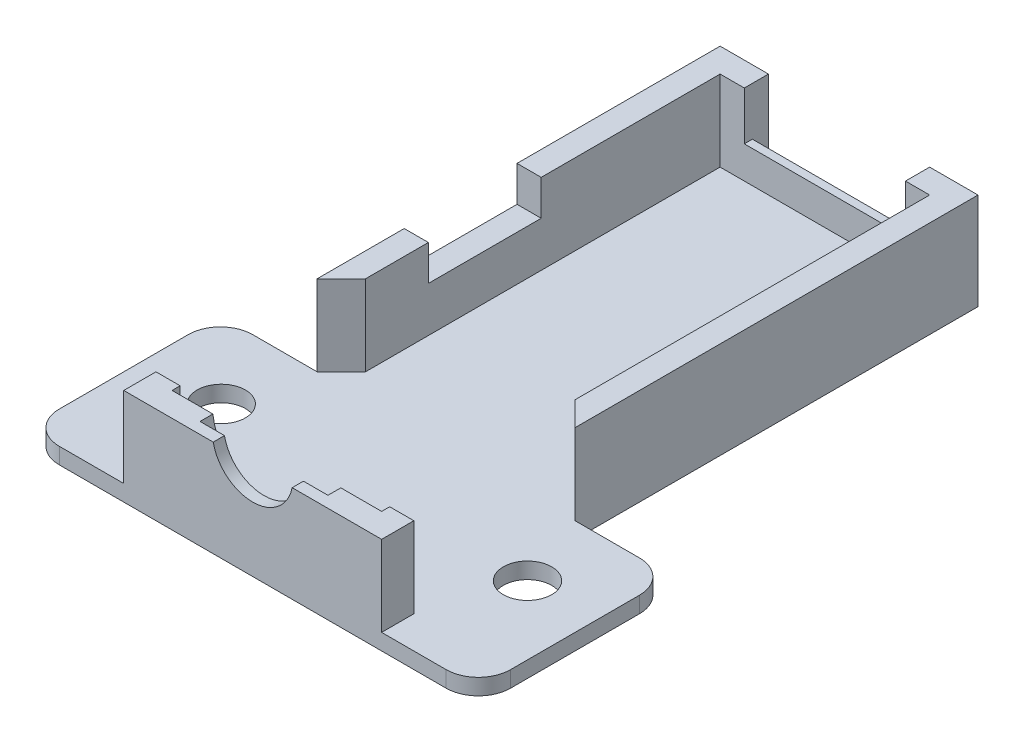
SolidWorks part; units mm, degrees
ref_plane "Front Plane" through (0, 0, 0) normal (0, 0, 1) x (1, 0, 0)
ref_plane "Top Plane" through (0, 0, 0) normal (0, 1, 0) x (1, 0, 0)
ref_plane "Right Plane" through (0, 0, 0) normal (1, 0, 0) x (0, 0, -1)
sketch "Sketch1" plane through (0, 0, 0) normal (0, 1, 0) x (1, 0, 0)
  line L1 (-6.5, 17) -> (6.5, 17)
  line L2 (-6.5, 17) -> (-6.5, -17)
  line L3 (-6.5, -17) -> (6.5, -17)
  line L4 (6.5, 17) -> (6.5, -17)
  line L5 (-6.5, 17) -> (6.5, -17) construction
  line L6 (-6.5, -17) -> (6.5, 17) construction
  line L7 (-8, 18.5) -> (8, 18.5)
  line L8 (-8, 18.5) -> (-8, -18.5)
  line L9 (-8, -18.5) -> (8, -18.5)
  line L10 (8, 18.5) -> (8, -18.5)
  line L11 (-8, 18.5) -> (8, -18.5) construction
  line L12 (-8, -18.5) -> (8, 18.5) construction
  point P0 (0, 0)
  point P6 (0, 0)
  dimension "D1" = 13
  dimension "D2" = 1.5
  dimension "D3" = 1.5
  dimension "D4" = 34
extrude "Boss-Extrude1" add sketch "Sketch1" along normal blind 5 contours L7 L10 L9 L8 | L2 L3 L4 L1
sketch "Sketch2" plane through (0, 0, 0) normal (0, -1, 0) x (1, 0, 0)
  line L1 (8, -18.5) -> (-8, -18.5)
  line L2 (8, -18.5) -> (8, 18.5)
  line L3 (8, 18.5) -> (-8, 18.5)
  line L4 (-8, -18.5) -> (-8, 18.5)
  line L5 (8, -18.5) -> (-8, 18.5) construction
  line L6 (8, 18.5) -> (-8, -18.5) construction
  point P0 (0, 0)
extrude "Boss-Extrude2" add sketch "Sketch2" along normal blind 1
sketch "Sketch3" plane through (8, 0, 0) normal (1, 0, 0) x (0, 0, -1)
  line L0 (18.5, 5) -> (-18.5, 5) construction
  line L1 (-16.5, 0) -> (-6.5, 0)
  line L2 (-16.5, 0) -> (-16.5, 5)
  line L3 (-16.5, 5) -> (-6.5, 5)
  line L4 (-6.5, 0) -> (-6.5, 5)
  line L5 (-18.5, 5) -> (-18.5, -1) construction
  dimension "D1" = 2
  dimension "D2" = 10
extrude "Cut-Extrude1" cut sketch "Sketch3" against normal blind 21
sketch "Sketch4" plane through (-8, 0, 0) normal (-1, 0, 0) x (0, 0, 1)
  line L0 (16.5, 0) -> (6.5, 0) construction
  line L1 (1.1, 2.8) -> (-5.9, 2.8)
  line L2 (1.1, 2.8) -> (1.1, 5)
  line L3 (1.1, 5) -> (-5.9, 5)
  line L4 (-5.9, 2.8) -> (-5.9, 5)
  line L5 (-18.5, 5) -> (6.5, 5) construction
  line L6 (6.5, 0) -> (6.5, 5) construction
  dimension "D1" = 2.8
  dimension "D2" = 0
  dimension "D3" = 7
  dimension "D4" = 5.4
extrude "Cut-Extrude2" cut sketch "Sketch4" against normal blind 2
sketch "Sketch5" plane through (0, 0, 18.5) normal (0, 0, 1) x (1, 0, 0)
  line L0 (8, -1) -> (-8, -1) construction
  circle A0 centre (0, 5.5) radius 2.5
  dimension "D1" = 5
  dimension "D2" = 6.5
extrude "Cut-Extrude3" cut sketch "Sketch5" against normal blind 2
sketch "Sketch6" plane through (0, 0, -17) normal (0, 0, 1) x (1, 0, 0)
  line L0 (-6.5, 5) -> (6.5, 5) construction
  line L1 (-5, 2) -> (5, 2)
  line L2 (-5, 2) -> (-5, 5)
  line L3 (-5, 5) -> (5, 5)
  line L4 (5, 2) -> (5, 5)
  line L5 (-6.5, 5) -> (-6.5, 0) construction
  line L6 (-6.5, 0) -> (6.5, 0) construction
  dimension "D1" = 10
  dimension "D2" = 1.5
  dimension "D3" = 2
extrude "Cut-Extrude4" cut sketch "Sketch6" against normal blind 2
chamfer "Chamfer1" distance 1 angle 45 1 edges at (0, 2, -18.5)
sketch "Sketch7" plane through (8, 0, 0) normal (1, 0, 0) x (0, 0, -1)
  line L1 (-18.5, -1) -> (-6.5, -1)
  line L2 (-18.5, -1) -> (-18.5, 0)
  line L3 (-18.5, 0) -> (-6.5, 0)
  line L4 (-6.5, -1) -> (-6.5, 0)
extrude "Boss-Extrude3" add sketch "Sketch7" along normal blind 6
sketch "Sketch8" plane through (-8, 0, 0) normal (-1, 0, 0) x (0, 0, 1)
  line L1 (18.5, -1) -> (6.5, -1)
  line L2 (18.5, -1) -> (18.5, 0)
  line L3 (18.5, 0) -> (6.5, 0)
  line L4 (6.5, -1) -> (6.5, 0)
extrude "Boss-Extrude4" add sketch "Sketch8" along normal blind 6
fillet "Fillet1" radius 2 4 edges at (-14, -0.5, 6.5) (14, -0.5, 6.5) (-14, -0.5, 18.5) (14, -0.5, 18.5)
sketch "Sketch9" plane through (0, 0, 0) normal (0, 1, 0) x (1, 0, 0)
  line L0 (14, -8.5) -> (14, -16.5) construction
  line L1 (12, -6.5) -> (8, -6.5) construction
  circle A0 centre (-9.25, -11.2) radius 1.5
  circle A1 centre (9.75, -11.2) radius 1.5
  dimension "D1" = 19
  dimension "D2" = 4.25
  dimension "D3" = 4.7
  dimension "D4" = 3
  dimension "D5" = 3
extrude "Cut-Extrude5" cut sketch "Sketch9" against normal blind 6
sketch "Sketch12" plane through (0, 0, 17) normal (0, 0, -1) x (-1, 0, 0)
  circle A0 centre (0, 5.5) radius 4
  dimension "D1" = 8
extrude "Cut-Extrude6" cut sketch "Sketch12" against normal blind 0.8
chamfer "Chamfer2" distance 1.5 angle 45 2 edges at (6.5, 2.5, 6.5) (-6.5, 2.5, 6.5)
